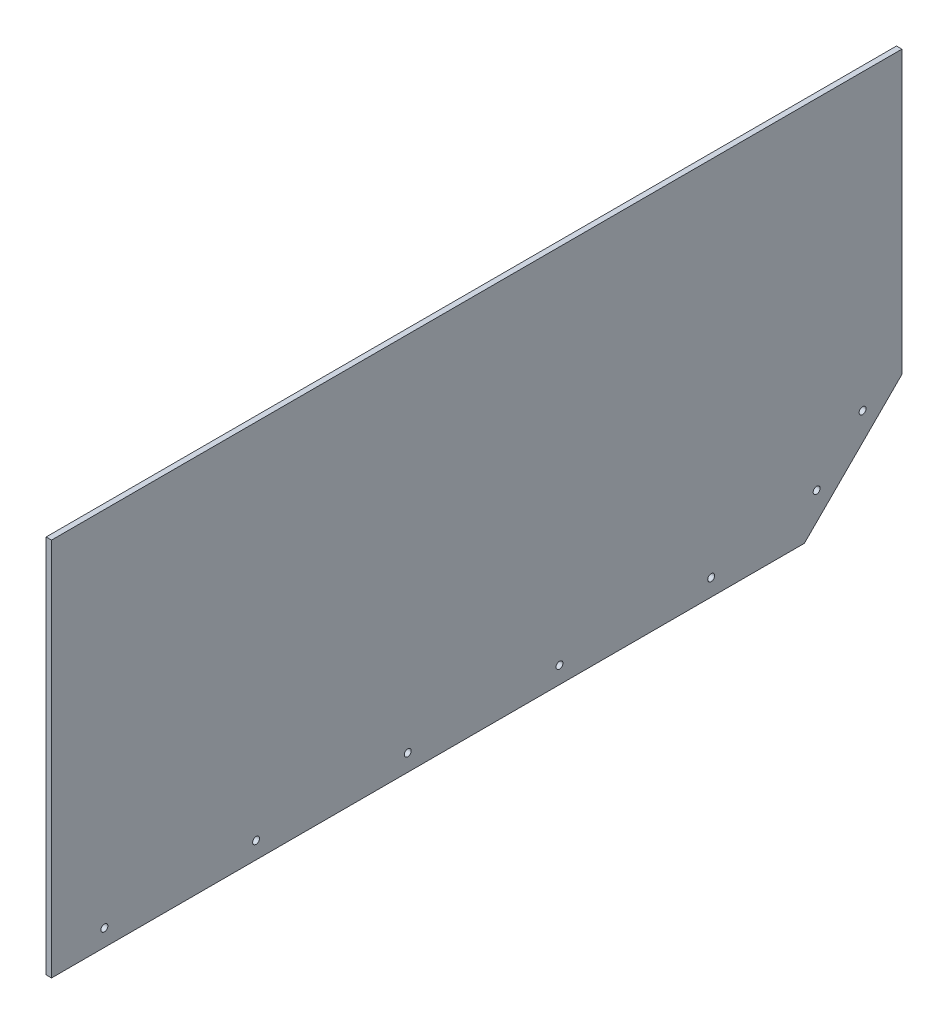
SolidWorks part; units mm, degrees
material "6061-T6 (SS)"
ref_plane "X-Y Datum" through (0, 0, 0) normal (0, 0, 1) x (1, 0, 0)
ref_plane "X-Z Datum" through (0, 0, 0) normal (0, 1, 0) x (1, 0, 0)
ref_plane "Y-Z Datum" through (0, 0, 0) normal (1, 0, 0) x (0, 0, -1)
sketch "Sketch1" plane through (0, 0, 0) normal (1, 0, 0) x (0, 0, -1)
  line L1 (-249.174, 82.55) -> (249.174, 82.55)
  line L2 (-249.174, 82.55) -> (-249.174, -82.55)
  line L3 (-249.174, -82.55) -> (249.174, -82.55)
  line L4 (249.174, 82.55) -> (249.174, -82.55)
  line L5 (-249.174, 82.55) -> (249.174, -82.55) construction
  line L6 (-249.174, -82.55) -> (249.174, 82.55) construction
  point P0 (0, 0)
  dimension "D1" = 165.1
  dimension "D2" = 498.348
extrude "Boss-Extrude1" add sketch "Sketch1" along normal mid plane 3.175
sketch "Sketch2" plane through (1.5875, 0, 0) normal (1, 0, 0) x (0, 0, -1)
  line L2 (249.174, -82.55) -> (192.024, -139.7)
  line L5 (-249.174, -82.55) -> (249.174, -82.55) construction
  line L6 (-249.174, -82.55) -> (249.174, -82.55)
  line L8 (192.024, -139.7) -> (-249.174, -139.7)
  line L9 (-249.174, -139.7) -> (-249.174, -82.55)
  line L11 (-249.174, 82.55) -> (-249.174, -82.55) construction
  line L12 (249.174, -82.55) -> (249.174, 82.55) construction
  line M10 (-249.174, -82.55) -> (249.174, -82.55)
  dimension "D1" = 45
  dimension "D5" = 57.15
extrude "Boss-Extrude2" add sketch "Sketch2" against normal blind 3.175 contours L2 M10 region at (1.5875, -110.5456, 13.9978)
sketch "Sketch3" plane through (-1.5875, 0, 0) normal (-1, 0, 0) x (0, 0, 1)
  line L0 (218.186, -139.7) -> (218.186, -129.794)
  line L1 (-192.024, -139.7) -> (249.174, -139.7) construction
  line L2 (218.186, -129.794) -> (249.174, -129.794)
  line L3 (249.174, 82.55) -> (249.174, -139.7) construction
  circle A0 centre (218.186, -129.794) radius 2.025
extrude "Cut-Extrude1" cut sketch "Sketch3" against normal through all contours L0 A0 L2 | L2 A0 L0 region at (-1.5875, -129.5075, 217.8995) region at (-1.5875, -130.6534, 219.0454)
pattern_linear "LPattern1" count 5 spacing 88.9 along (0, 0, -1) of "Cut-Extrude1"
sketch "Sketch4" plane through (-1.5875, 0, 0) normal (-1, 0, 0) x (0, 0, 1)
  line L0 (-207.2904, -124.4336) -> (-199.2082, -116.3513)
  line L1 (-249.174, -82.55) -> (-192.024, -139.7) construction
  line L2 (-192.024, -139.7) -> (-183.9418, -131.6178)
  line L3 (-183.9418, -131.6178) -> (-199.2082, -116.3513)
  circle A0 centre (-199.2082, -116.3513) radius 2.025
extrude "Cut-Extrude2" cut sketch "Sketch4" against normal through all and the other way through all contours L3 A0 L0 | L0 A0 L3 region at (-1.5875, -115.9462, -199.2082) region at (-1.5875, -117.5668, -199.2082)
pattern_linear "LPattern2" count 2 spacing 38.1 along (0, 0.7071, -0.7071) of "Cut-Extrude2"
